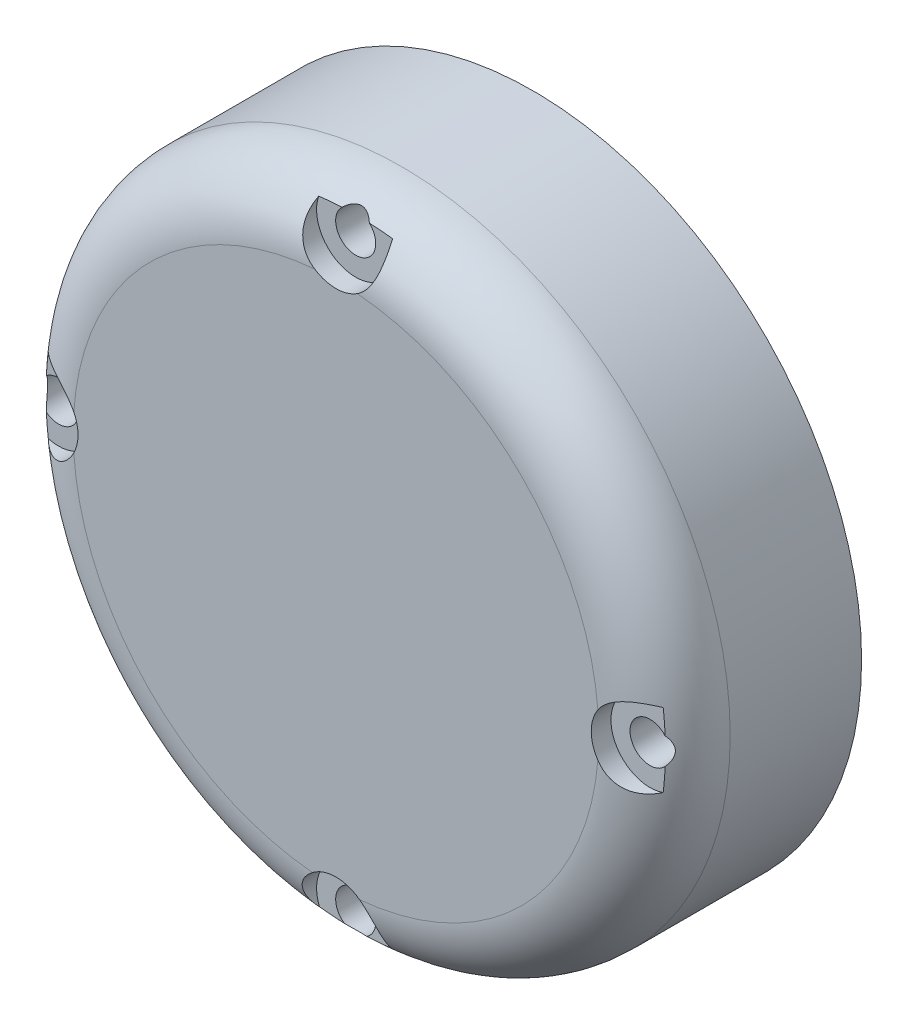
SolidWorks part; units mm, degrees
ref_plane "Front Plane" through (0, 0, 0) normal (0, 0, 1) x (1, 0, 0)
ref_plane "Top Plane" through (0, 0, 0) normal (0, 1, 0) x (1, 0, 0)
ref_plane "Right Plane" through (0, 0, 0) normal (1, 0, 0) x (0, 0, -1)
sketch "Sketch1" plane through (0, 0, 0) normal (0, 0, 1) x (1, 0, 0)
  circle A0 centre (0, 0) radius 19
  circle A1 centre (0, 0) radius 25
  dimension "D1" = 50
  dimension "D2" = 38
extrude "Boss-Extrude1" add sketch "Sketch1" along normal blind 5
sketch "Sketch2" plane through (0, 0, 5) normal (0, 0, 1) x (1, 0, 0)
  circle A0 centre (0, 0) radius 25 construction
  circle A1 centre (0, 0) radius 25
extrude "Boss-Extrude2" add sketch "Sketch2" along normal blind 10
fillet "Fillet1" radius 5 2 edges at (19, 0, 5) (25, 0, 15)
hole_wizard "CBORE for #3 Binding Head Machine Screw1" positions "Sketch13" profile "Sketch14" counterbore size "#3" standard "ANSI Inch" end condition through all
sketch "Sketch13" plane through (0, 0, 15) normal (0, 0, 1) x (1, 0, 0)
  circle A0 centre (0, 0) radius 20 construction
  point P0 (0, 22.4351)
  point P2 (0, -22.2959)
  point P4 (22.4003, 0)
  point P6 (-22.609, 0)
  dimension "D1" = 22.4003
  dimension "D2" = 22.609
  dimension "D3" = 22.4351
  dimension "D4" = 22.2959
sketch "Sketch14" plane through (0, 22.4351, 15) normal (1, 0, 0) x (0, -1, 0)
  line L0 (0, 0) -> (0, 15)
  line L1 (0, 15) -> (1.524, 15)
  line L3 (1.524, 15) -> (1.524, 1.4986)
  line L4 (1.524, 1.4986) -> (2.9769, 1.4986)
  line L5 (2.9769, 1.4986) -> (2.9769, 0)
  line L7 (2.9769, 0) -> (0, 0)
  line L11 (0, -6.35) -> (0, 107.95) construction
  dimension "Thru Hole Dia." = 3.048
  dimension "Thru Hole Depth" = 15
  dimension "C'Bore Dia." = 5.9538
  dimension "C'Bore Depth" = 1.4986
